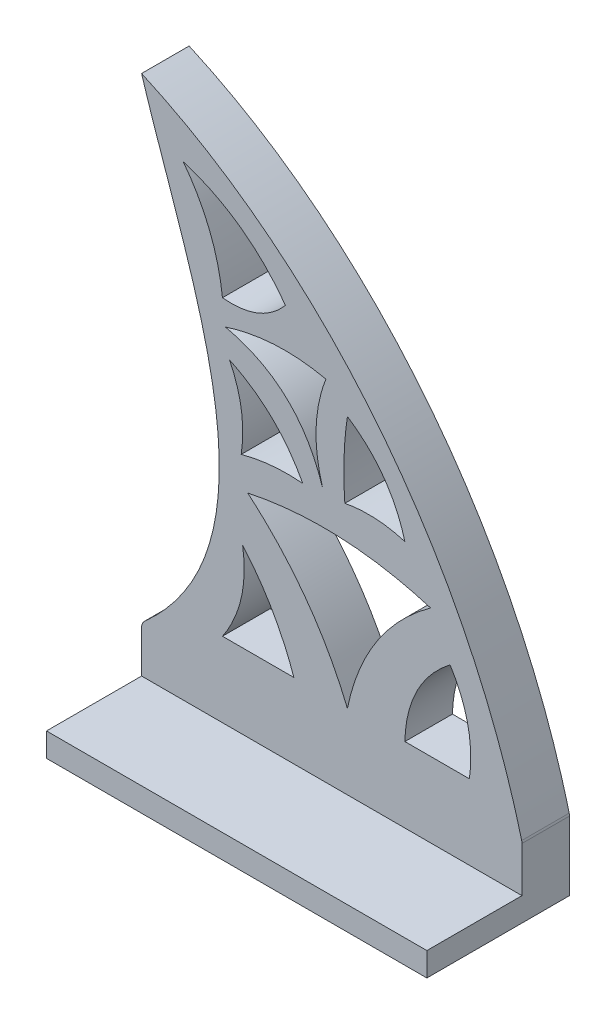
SolidWorks part; units mm, degrees
material "1060 Alloy"
ref_plane "Front Plane" through (0, 0, 0) normal (0, 0, 1) x (1, 0, 0)
ref_plane "Top Plane" through (0, 0, 0) normal (0, 1, 0) x (1, 0, 0)
ref_plane "Right Plane" through (0, 0, 0) normal (1, 0, 0) x (0, 0, -1)
sketch "Sketch1" plane through (0, 0, 0) normal (0, 0, 1) x (1, 0, 0)
  line L1 (0, 0) -> (101.6, 0)
  line L2 (0, 0) -> (0, 152.4)
  line L3 (0, 152.4) -> (101.6, 152.4)
  line L4 (101.6, 0) -> (101.6, 152.4)
  dimension "D1" = 101.6
  dimension "D2" = 152.4
extrude "Boss-Extrude1" add sketch "Sketch1" along normal blind 12.7 contours L2 L1 L4 L3
sketch "Sketch2" plane through (0, 0, 0) normal (0, 0, 1) x (1, 0, 0)
  line L0 (0, 152.4) -> (0, 279.4) construction
  line L1 (0, 152.4) -> (101.6, 152.4)
  line L3 (40.6766, 160.02) -> (21.6029, 160.02)
  line L4 (70.3278, 160.02) -> (87.5465, 160.02)
  spline S0 degree 3 poles (0, 279.4) (51.2861, 256.55) (87.8369, 205.9579) (101.6, 152.4) knots 0 0 0 0 1 1 1 1
  spline S1 degree 3 poles (0, 152.4) (39.7901, 186.8391) (12.3098, 238.8455) (0, 279.4) knots 0 0 0 0 1 1 1 1
  spline S2 degree 2 poles (26.9805, 183.8137) (28.9588, 170.8375) (21.6029, 160.02) knots 0 0 0 1 1 1
  spline S3 degree 2 poles (82.3961, 183.8137) (89.3396, 172.7738) (87.5465, 160.02) knots 0 0 0 1 1 1
  spline S4 degree 2 poles (23.5161, 224.8619) (28.2353, 215.2193) (26.6057, 204.5822) knots 0 0 0 1 1 1
  spline S5 degree 2 poles (54.9771, 227.5573) (66.6459, 219.8522) (70.3283, 206.2775) knots 0 0 0 1 1 1
  spline S6 degree 2 poles (21.6029, 238.3231) (31.8648, 237.2845) (38.4123, 244.9499) knots 0 0 0 1 1 1
  spline S7 degree 2 poles (26.9805, 183.8137) (36.1385, 173.1751) (40.6766, 160.02) knots 0 0 0 1 1 1
  spline S8 degree 2 poles (82.3961, 183.8137) (70.6714, 174.6636) (70.3278, 160.02) knots 0 0 0 1 1 1
  spline S9 degree 2 poles (54.9771, 160.02) (46.0835, 181.5476) (28.3421, 196.5298) knots 0 0 0 1 1 1
  spline S10 degree 2 poles (54.9771, 160.02) (59.3747, 181.4006) (77.1872, 194.3635) knots 0 0 0 1 1 1
  spline S11 degree 2 poles (28.3421, 196.5298) (53.0178, 201.7323) (77.1872, 194.3635) knots 0 0 0 1 1 1
  spline S12 degree 2 poles (26.6057, 204.5822) (34.7004, 206.7929) (43.0535, 206.088) knots 0 0 0 1 1 1
  spline S13 degree 2 poles (43.0535, 206.088) (36.2398, 218.9127) (23.5161, 224.8619) knots 0 0 0 1 1 1
  spline S14 degree 2 poles (70.3283, 206.2775) (62.3616, 208.669) (54.2871, 207.1099) knots 0 0 0 1 1 1
  spline S15 degree 2 poles (54.2871, 207.1099) (53.4821, 217.3917) (54.9771, 227.5573) knots 0 0 0 1 1 1
  spline S16 degree 2 poles (48.4004, 207.5354) (42.0542, 227.5662) (22.3756, 231.9373) knots 0 0 0 1 1 1
  spline S17 degree 2 poles (48.4004, 207.5354) (44.3936, 220.7345) (49.2258, 233.3158) knots 0 0 0 1 1 1
  spline S18 degree 2 poles (49.2258, 233.3158) (35.6412, 236.2679) (22.3756, 231.9373) knots 0 0 0 1 1 1
  spline S19 degree 2 poles (21.6029, 238.3231) (19.952, 252.9745) (11.0947, 264.6015) knots 0 0 0 1 1 1
  spline S20 degree 2 poles (11.0947, 264.6015) (28.0538, 259.2958) (38.4123, 244.9499) knots 0 0 0 1 1 1
  dimension "D1" = 127
extrude "Boss-Extrude3" add sketch "Sketch2" along normal blind 12.7 contours S1 L1 S0 S18 S17 S16 S13 S12 S4 S8 S3 L4 S2 S7 L3 S9 S11 S10 S14 S15 S5 S19 S20 S6 region at (45.9671, 198.7592, 0)
fillet "Fillet1" radius 2.54 2 edges at (101.6, 152.4, 6.35) (0, 152.4, 6.35)
fillet "Fillet2" radius 5.08 2 edges at (101.6, 0, 6.35) (0, 0, 6.35)
sketch "Sketch5" plane through (0, 0, 12.7) normal (0, 0, 1) x (1, 0, 0)
  line L1 (101.519, 133.6639) -> (101.6, 133.6639)
  line L2 (101.6, 5.08) -> (101.6, 152.0778) construction
  line L4 (101.6, 133.6639) -> (0, 133.6639)
  line L5 (101.6, 133.6639) -> (101.6, 0)
  line L6 (101.6, 0) -> (0, 0)
  line L7 (0, 133.6639) -> (0, 0)
  line M2 (5.08, 0) -> (96.52, 0)
  arc M3 (96.52, 0) -> (101.6, 5.08) centre (96.52, 5.08) ccw
  line M4 (101.6, 5.08) -> (101.6, 152.0778)
  line M9 (0, 151.2513) -> (0, 5.08)
  arc M10 (0, 5.08) -> (5.08, 0) centre (5.08, 5.08) ccw
extrude "Cut-Extrude2" cut sketch "Sketch5" against normal through all contours L1 L4 M9 M10 M2 M3 M4 region at (50.8, 66.8856, 12.7)
sketch "Sketch8" plane through (0, 0, 12.7) normal (0, 0, 1) x (1, 0, 0)
  line L0 (0, 133.6639) -> (0, 151.2513) construction
  line L1 (101.6, 133.6639) -> (0, 133.6639)
  line L2 (101.6, 133.6639) -> (101.6, 140.0139)
  line L3 (101.6, 140.0139) -> (0, 140.0139)
  line L4 (0, 133.6639) -> (0, 140.0139)
  dimension "D1" = 6.35
extrude "Boss-Extrude4" add sketch "Sketch8" along normal blind 25.4
